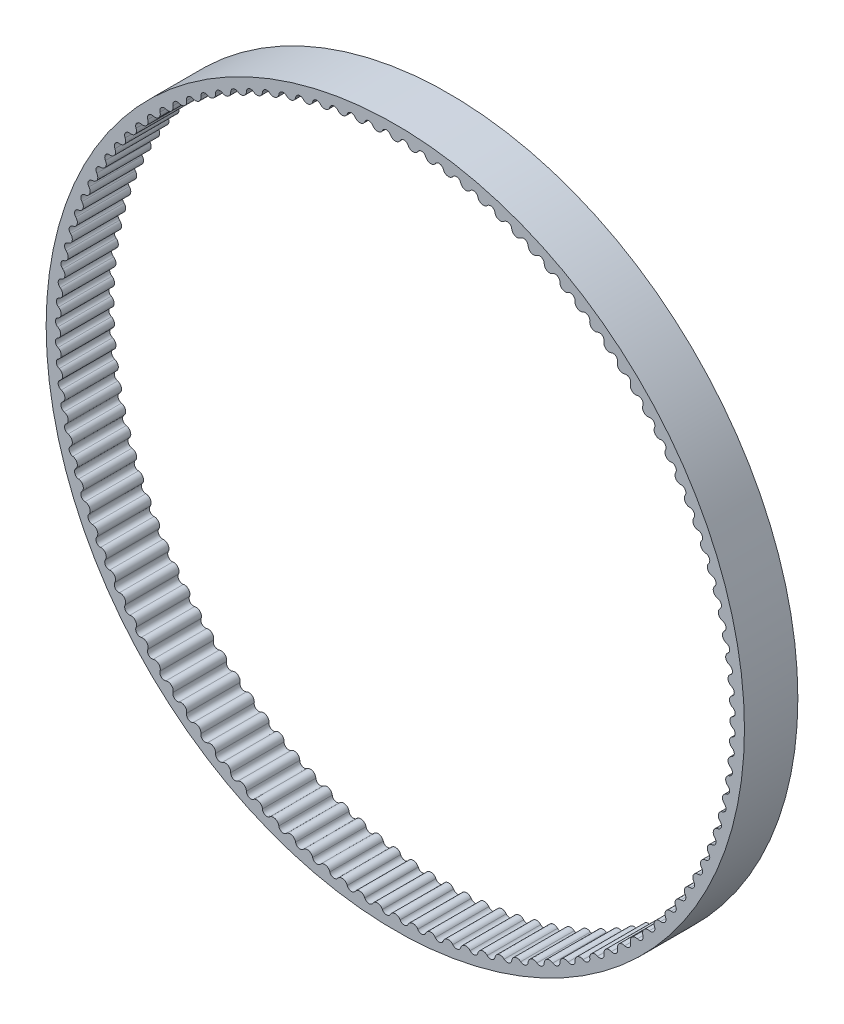
SolidWorks part; units mm, degrees
ref_plane "Front Plane" through (0, 0, 0) normal (0, 0, 1) x (1, 0, 0)
ref_plane "Top Plane" through (0, 0, 0) normal (0, 1, 0) x (1, 0, 0)
ref_plane "Right Plane" through (0, 0, 0) normal (1, 0, 0) x (0, 0, -1)
sketch "Sketch1" plane through (0, 0, 0) normal (0, 0, 1) x (1, 0, 0)
  line L0 (0, 0) -> (0, 38.1972) construction
  line L1 (0, 0) -> (1.9991, 38.1449) construction
  line L2 (0, 0) -> (3.9927, 37.988) construction
  line L3 (-1.9991, 38.1449) -> (0, 0) construction
  circle A0 centre (0, 0) radius 39.2272
  circle A1 centre (0, 0) radius 37.5872
  circle A2 centre (0, 0) radius 38.1972 construction
  circle A10 centre (0, 38.1972) radius 0.61
  circle A101 centre (1.9991, 38.1449) radius 0.61
  circle A102 centre (0.9867, 37.6805) radius 0.5038
  circle A103 centre (-0.9867, 37.6805) radius 0.5038
  circle A104 centre (-1.9991, 38.1449) radius 0.61
  point P16 (-1.9672, 37.5357)
  point P17 (0, 37.5872)
  point P77 (0, 0)
  dimension "Tooth Diameter" = 1.22
  dimension "Pitch Diameter" = 76.3944
  dimension "Belt Thickness" = 1.64
  dimension "Angle" = 3
  dimension "D3" = 3
sketch "Sketch2" plane through (0, 0, 0) normal (0, 0, 1) x (1, 0, 0)
  circle A0 centre (0, 0) radius 37.5872 construction
  circle A1 centre (0, 0) radius 39.2272 construction
  circle A2 centre (0, 0) radius 37.5872
  circle A3 centre (0, 0) radius 39.2272
extrude "Boss-Extrude1" add sketch "Sketch2" along normal mid plane 6
sketch "Sketch3" plane through (0, 0, 0) normal (0, 0, 1) x (1, 0, 0)
  circle A0 centre (0, 0) radius 37.5872 construction
  circle A1 centre (1.9991, 38.1449) radius 0.61 construction
  circle A2 centre (0.9867, 37.6805) radius 0.5038 construction
  circle A3 centre (0, 38.1972) radius 0.61 construction
  arc A4 (1.9672, 37.5357) -> (0, 37.5872) centre (0, 0) ccw
  arc A5 (1.4446, 37.8905) -> (1.9672, 37.5357) centre (1.9991, 38.1449) ccw
  arc A6 (1.4446, 37.8905) -> (0.5404, 37.9142) centre (0.9867, 37.6805) ccw
  arc A7 (0, 37.5872) -> (0.5404, 37.9142) centre (0, 38.1972) ccw
extrude "Cut-Extrude1" cut sketch "Sketch3" against normal through all both and the other way through all
pattern_circular "CirPattern3" count 120 over 360 about axis through (0, 0, 3) along (0, 0, -1) of "Cut-Extrude1"
ref_axis "Center Axis 1" through (0, 0, 3) along (0, 0, -1)
equation "\"D3@Sketch1\" = \"Angle@Sketch1\""
